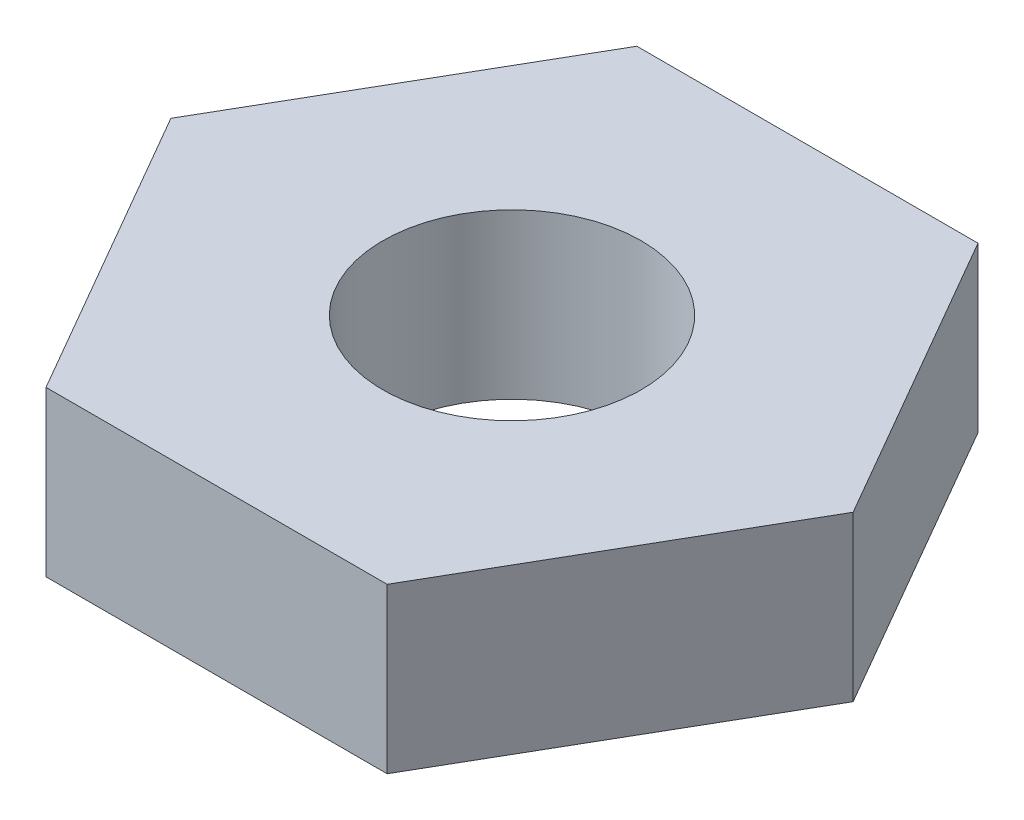
SolidWorks part; units mm, degrees
ref_plane "Front Plane" through (0, 0, 0) normal (0, 0, 1) x (1, 0, 0)
ref_plane "Top Plane" through (0, 0, 0) normal (0, 1, 0) x (1, 0, 0)
ref_plane "Right Plane" through (0, 0, 0) normal (1, 0, 0) x (0, 0, -1)
sketch "Sketch1" plane through (0, 0, 0) normal (0, 1, 0) x (1, 0, 0)
  line L1 (3.9606, 0) -> (1.9803, 3.43)
  line L2 (1.9803, 3.43) -> (-1.9803, 3.43)
  line L3 (-1.9803, 3.43) -> (-3.9606, 0)
  line L4 (-3.9606, 0) -> (-1.9803, -3.43)
  line L5 (-1.9803, -3.43) -> (1.9803, -3.43)
  line L6 (1.9803, -3.43) -> (3.9606, 0)
  circle A0 centre (0, 0) radius 3.43 construction
  circle A1 centre (0, 0) radius 1.5
  dimension "D1" = 6.86
  dimension "D2" = 3
extrude "Boss-Extrude1" add sketch "Sketch1" along normal blind 1.905 contours L5 L6 L1 L2 L3 L4 A1 region at (2.8797, 0, 1.6626)
